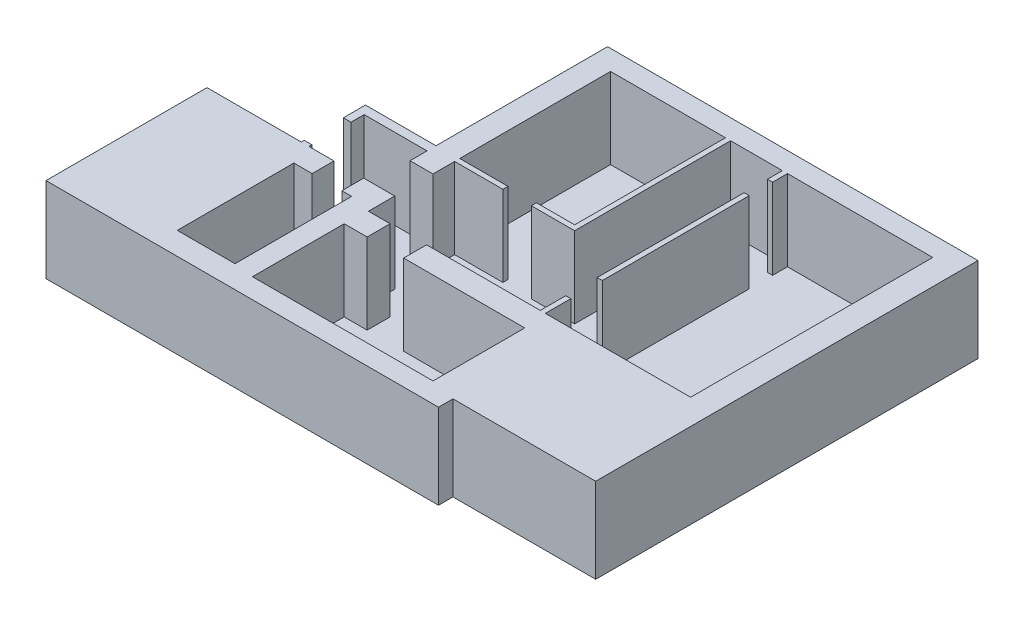
SolidWorks part; units mm, degrees
ref_plane "Спереди" through (0, 0, 0) normal (0, 0, 1) x (1, 0, 0)
ref_plane "Сверху" through (0, 0, 0) normal (0, 1, 0) x (1, 0, 0)
ref_plane "Справа" through (0, 0, 0) normal (1, 0, 0) x (0, 0, -1)
sketch "Эскиз1" plane through (0, 0, 0) normal (0, 1, 0) x (1, 0, 0)
  line L1 (-12600, 0) -> (-12600, 3790)
  line L2 (-12600, 3790) -> (-10380, 3790)
  line L3 (-10380, 3790) -> (-10380, 3860)
  line L4 (-10380, 5300) -> (-8720, 5300)
  line L5 (-8720, 5300) -> (-8720, 9340)
  line L6 (-8720, 9340) -> (0, 9340)
  line L7 (0, 9340) -> (0, 2250)
  line L8 (0, 2250) -> (-2025, 2250) construction
  line L9 (-2025, 2250) -> (-2025, 0) construction
  line L10 (-2025, 2250) -> (-3395, 2250) construction
  line L11 (-3395, 2250) -> (-3395, 0) construction
  line L12 (-9310, 5300) -> (-9310, 6480) construction
  line L13 (-9310, 6480) -> (-8720, 6480) construction
  line L14 (-2285, 2250) -> (-2285, 1725) construction
  line L15 (-2285, 1725) -> (-2025, 1725) construction
  line L16 (-2025, 350) -> (-2375, 350) construction
  line L17 (-2375, 350) -> (-2375, 0) construction
  line L18 (-9610, 3790) -> (-9610, 3275)
  line L19 (-9610, 3275) -> (-10040, 3275)
  line L20 (-10040, 3275) -> (-10040, 530)
  line L21 (-10040, 530) -> (-8680, 530)
  line L22 (-8680, 530) -> (-8680, 3275)
  line L23 (-8680, 3275) -> (-8910, 3275)
  line L24 (-8910, 3275) -> (-8910, 3790)
  line L25 (-9610, 3790) -> (-10200, 3790)
  line L26 (-10380, 3860) -> (-10200, 3860)
  line L27 (-10200, 3860) -> (-10200, 3790)
  line L28 (-10380, 4780) -> (-10200, 4780)
  line L29 (-10200, 4780) -> (-10200, 5090)
  line L30 (-10200, 5090) -> (-8720, 5090)
  line L31 (-8720, 5090) -> (-8720, 4690)
  line L32 (-10380, 4780) -> (-10380, 5300)
  line L33 (-8720, 4690) -> (-8180, 4690)
  line L34 (-8180, 4690) -> (-8180, 5200)
  line L35 (-8910, 3790) -> (-8180, 3790)
  line L36 (-6810, 2630) -> (-3960, 2630)
  line L37 (-3960, 2630) -> (-3960, 470)
  line L38 (-8180, 3790) -> (-8180, 3170)
  line L39 (-8180, 3170) -> (-7670, 3170)
  line L40 (-7670, 3170) -> (-7670, 2630)
  line L41 (-6810, 2630) -> (-6810, 3170)
  line L42 (-6810, 3170) -> (-4135, 3170)
  line L43 (-7670, 2630) -> (-8210, 2630)
  line L44 (-8210, 2630) -> (-8210, 470)
  line L45 (-8210, 470) -> (-3960, 470)
  line L46 (-4135, 7970) -> (-4135, 4510)
  line L47 (-8180, 5200) -> (-7045, 5200)
  line L49 (-7045, 5200) -> (-7045, 5320)
  line L50 (-7045, 5320) -> (-8180, 5320)
  line L51 (-8180, 5320) -> (-8180, 8870)
  line L52 (-8180, 8870) -> (-5475, 8870)
  line L53 (-5475, 8870) -> (-5475, 5320)
  line L54 (-5475, 5320) -> (-6375, 5320)
  line L55 (-6375, 5320) -> (-6375, 5200)
  line L56 (-6375, 5200) -> (-5355, 5200)
  line L57 (-4015, 4510) -> (-4015, 7970)
  line L58 (-595, 3170) -> (-595, 8870)
  line L59 (-4135, 3170) -> (-4135, 3770)
  line L60 (-4135, 3770) -> (-4015, 3770)
  line L61 (-4015, 3770) -> (-4015, 3170)
  line L62 (-4015, 3170) -> (-595, 3170)
  line L63 (-4135, 4510) -> (-4015, 4510)
  line L64 (-4015, 7970) -> (-4135, 7970)
  line L65 (-595, 8870) -> (-4015, 8870)
  line L66 (-4015, 8870) -> (-4015, 8520)
  line L67 (-4015, 8520) -> (-4135, 8520)
  line L68 (-4135, 8520) -> (-4135, 8870)
  line L69 (-4135, 8870) -> (-5355, 8870)
  line L70 (-5355, 8870) -> (-5355, 5200)
  line L71 (-3360, 0) -> (-3360, 340)
  line L72 (0, 2250) -> (0, 340)
  line L74 (-3360, 340) -> (0, 340)
  line L75 (-3360, 0) -> (-12600, 0)
  line L76 (-3395, 0) -> (0, 0) construction
  line L77 (0, 0) -> (0, 340) construction
  dimension "D1" = 8720
  dimension "D3" = 2250
  dimension "D4" = 2025
  dimension "D5" = 9205
  dimension "D6" = 3880
  dimension "D7" = 3790
  dimension "D8" = 2220
  dimension "D9" = 1510
  dimension "D10" = 120
  dimension "D11" = 525
  dimension "D12" = 260
  dimension "D13" = 350
  dimension "D14" = 590
  dimension "D15" = 1180
  dimension "D16" = 700
  dimension "D17" = 3260
  dimension "D18" = 1360
  dimension "D19" = 770
  dimension "D20" = 515
  dimension "D21" = 1300
  dimension "D22" = 180
  dimension "D23" = 310
  dimension "D24" = 920
  dimension "D25" = 430
  dimension "D26" = 1220
  dimension "D27" = 900
  dimension "D28" = 4250
  dimension "D29" = 540
  dimension "D30" = 620
  dimension "D31" = 540
  dimension "D32" = 510
  dimension "D33" = 860
  dimension "D34" = 540
  dimension "D35" = 2160
  dimension "D36" = 4045
  dimension "D37" = 2030
  dimension "D38" = 900
  dimension "D39" = 3420
  dimension "D40" = 3540
  dimension "D41" = 670
  dimension "D42" = 3360
  dimension "D43" = 600
  dimension "D44" = 1340
  dimension "D45" = 5700
  dimension "D46" = 350
  dimension "D47" = 900
  dimension "D48" = 340
  dimension "D51" = 2705
  dimension "D53" = 920
extrude "Бобышка-Вытянуть1" add sketch "Эскиз1" along normal blind 1900
sketch "Эскиз2" plane through (0, 0, 0) normal (0, -1, 0) x (1, 0, 0)
  line L0 (0, -9340) -> (-8720, -9340) construction
  line L1 (0, -9340) -> (-8720, -9340)
  line L2 (0, -340) -> (0, -9340) construction
  line L3 (0, -340) -> (0, -9340)
  line L4 (-12600, 0) -> (-3360, 0) construction
  line L8 (-12600, 0) -> (-3360, 0)
  line L10 (-8720, -9340) -> (-8720, -5300) construction
  line L11 (-8720, -5300) -> (-10380, -5300) construction
  line L12 (-10380, -5300) -> (-10380, -4780) construction
  line L13 (-10380, -3790) -> (-12600, -3790) construction
  line L14 (-12600, -3790) -> (-12600, 0) construction
  line L15 (-8720, -9340) -> (-8720, -5300)
  line L16 (-8720, -5300) -> (-10380, -5300)
  line L17 (-10380, -5300) -> (-10380, -3790)
  line L18 (-10380, -3790) -> (-12600, -3790)
  line L19 (-12600, -3790) -> (-12600, 0)
  line L20 (-3360, -340) -> (0, -340) construction
  line L21 (-3360, -340) -> (0, -340)
  line L22 (-3360, 0) -> (-3360, -340) construction
  line L23 (-3360, 0) -> (-3360, -340)
extrude "Бобышка-Вытянуть2" add sketch "Эскиз2" along normal blind 100
ref_plane "Плоскость1" through (0, 1100, 0) normal (0, 1, 0) x (1, 0, 0)
ref_axis "Ось1" through (-3360, 1100, 0) along (-1, 0, 0)
ref_axis "Ось2" through (0, 1100, -9340) along (0, 0, 1)
ref_point "Точка1"
